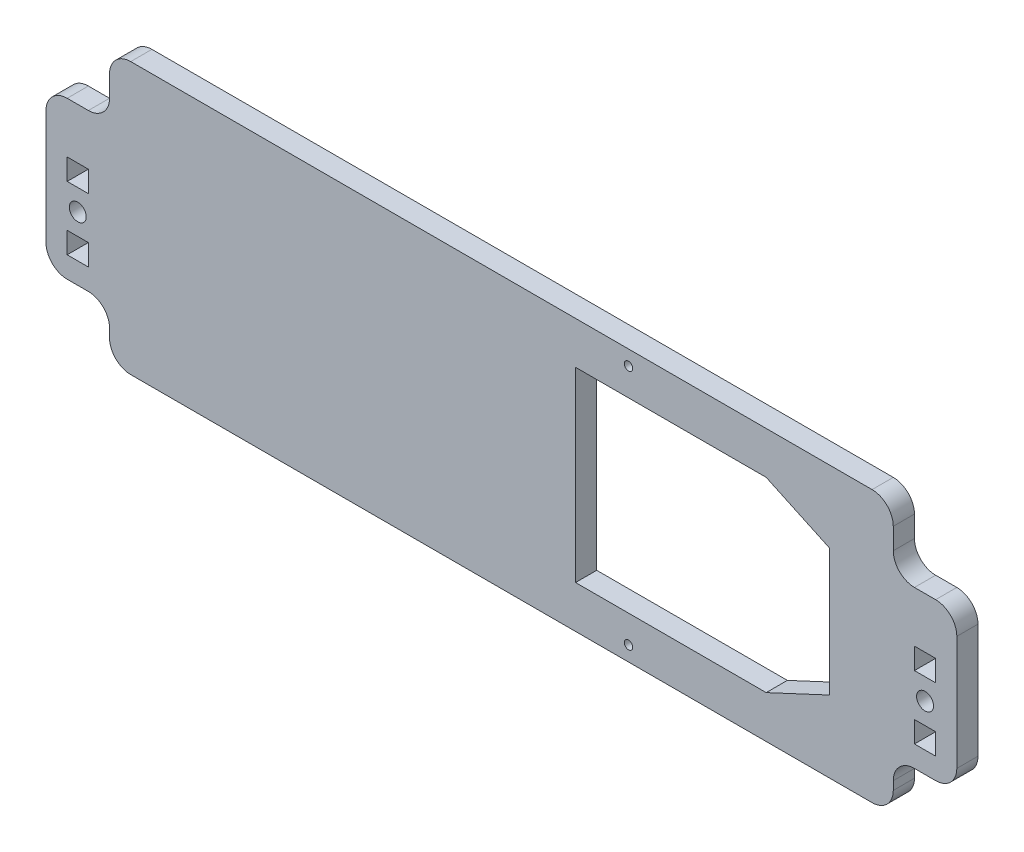
SolidWorks part; units mm, degrees
ref_plane "Plan de face" through (0, 0, 0) normal (0, 0, 1) x (1, 0, 0)
ref_plane "Plan de dessus" through (0, 0, 0) normal (0, 1, 0) x (1, 0, 0)
ref_plane "Plan de droite" through (0, 0, 0) normal (1, 0, 0) x (0, 0, -1)
sketch "Esquisse1" plane through (0, 0, 0) normal (0, 0, 1) x (1, 0, 0)
  line L0 (0, 0) -> (0, 34.7641) construction
  line L1 (0, 0) -> (100, 0) construction
  line L2 (-107.5, 17) -> (-107.5, -20)
  line L3 (-107.5, 32) -> (107.5, 32) construction
  line L4 (-107.5, 32) -> (-107.5, -32) construction
  line L5 (-107.5, -32) -> (107.5, -32) construction
  line L6 (107.5, 32) -> (107.5, -32) construction
  line L7 (-107.5, -20) -> (-92.5, -20)
  line L8 (-92.5, -20) -> (-92.5, -32)
  line L9 (-92.5, -32) -> (92.5, -32)
  line L10 (92.5, -32) -> (92.5, -20)
  line L11 (92.5, -20) -> (107.5, -20)
  line L12 (107.5, -20) -> (107.5, 17)
  line L13 (107.5, 17) -> (92.5, 17)
  line L14 (92.5, 17) -> (92.5, 32)
  line L15 (92.5, 32) -> (-92.5, 32)
  line L16 (-92.5, 32) -> (-92.5, 17)
  line L17 (-92.5, 17) -> (-107.5, 17)
  line L18 (62.5, 22) -> (77.5, 15)
  line L19 (17.5, 22) -> (62.5, 22)
  line L20 (17.5, 22) -> (17.5, -22)
  line L21 (17.5, -22) -> (62.5, -22)
  line L22 (62.5, 22) -> (62.5, -22) construction
  line L23 (77.5, 15) -> (77.5, -15)
  line L24 (77.5, -15) -> (62.5, -22)
  circle A0 centre (30, 28.5) radius 1
  circle A1 centre (30, -28.5) radius 1
  point P28 (0, 0)
  line B0 (97.5, -10) -> (97.5, -15)
  line B1 (97.5, -10) -> (102.5, -10)
  line B2 (102.5, -10) -> (102.5, -15)
  line B3 (97.5, -15) -> (102.5, -15)
  line B4 (97.5, 0) -> (97.5, 5)
  line B5 (97.5, 0) -> (102.5, 0)
  line B6 (102.5, 0) -> (102.5, 5)
  line B7 (97.5, 5) -> (102.5, 5)
  line B8 (100, -5) -> (93.0276, -5) construction
  circle B9 centre (100, -5) radius 2
  line B10 (-97.5, -10) -> (-97.5, -15)
  line B11 (-97.5, -10) -> (-102.5, -10)
  line B12 (-102.5, -10) -> (-102.5, -15)
  line B13 (-97.5, -15) -> (-102.5, -15)
  line B14 (-97.5, 0) -> (-97.5, 5)
  line B15 (-97.5, 0) -> (-102.5, 0)
  line B16 (-102.5, 0) -> (-102.5, 5)
  line B17 (-97.5, 5) -> (-102.5, 5)
  circle B18 centre (-100, -5) radius 2
  dimension "D8" = 57
  dimension "D9" = 2
  dimension "D1" = 5
  dimension "D2" = 5
  dimension "D3" = 64
  dimension "D4" = 15
  dimension "D5" = 15
  dimension "D6" = 195
  dimension "D7" = 5
  dimension "D10" = 30
  dimension "D11" = 44
  dimension "D12" = 32.5
  dimension "D13" = 45
  dimension "D14" = 15
  dimension "D15" = 30
sketch_block_instance "Trou M4 plots 5mm-4"
sketch_block "Trou M4 plots 5mm" parameters "D2"=4, "D1"=5, "D3"=5, "D4"=10
sketch_block_instance "Trou M4 plots 5mm-5"
extrude "Boss.-Extru.1" add sketch "Esquisse1" along normal blind 5
fillet "Congé1" radius 5 12 edges at (-92.5, -20, 2.5) (-92.5, 17, 2.5) (92.5, 17, 2.5) (92.5, -20, 2.5) (107.5, -20, 2.5) (107.5, 17, 2.5) (92.5, -32, 2.5) (-92.5, -32, 2.5) (-107.5, -20, 2.5) (-107.5, 17, 2.5) (-92.5, 32, 2.5) (92.5, 32, 2.5)
